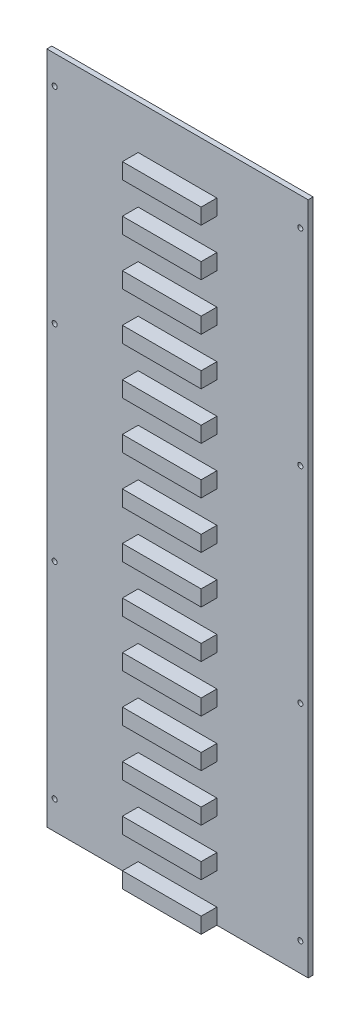
SolidWorks part; units mm, degrees
ref_plane "Front Plane" through (0, 0, 0) normal (0, 0, 1) x (1, 0, 0)
ref_plane "Top Plane" through (0, 0, 0) normal (0, 1, 0) x (1, 0, 0)
ref_plane "Right Plane" through (0, 0, 0) normal (1, 0, 0) x (0, 0, -1)
sketch "Sketch1" plane through (0, 0, 0) normal (0, 0, 1) x (1, 0, 0)
  line L1 (-41.5, -107) -> (41.5, -107)
  line L2 (-41.5, -107) -> (-41.5, 107)
  line L3 (-41.5, 107) -> (41.5, 107)
  line L4 (41.5, -107) -> (41.5, 107)
  line L5 (-41.5, -107) -> (41.5, 107) construction
  line L6 (-41.5, 107) -> (41.5, -107) construction
  point P0 (0, 0)
  dimension "D1" = 83
  dimension "D2" = 214
extrude "Boss-Extrude1" add sketch "Sketch1" along normal blind 1.5875
sketch "Sketch2" plane through (0, 0, 1.5875) normal (0, 0, 1) x (1, 0, 0)
  line L0 (0, -107) -> (0, 107) construction
  line L1 (-12.5, 88) -> (12.5, 88)
  line L2 (-12.5, 88) -> (-12.5, 93)
  line L3 (-12.5, 93) -> (12.5, 93)
  line L4 (12.5, 88) -> (12.5, 93)
  line L5 (-12.5, 88) -> (12.5, 93) construction
  line L6 (-12.5, 93) -> (12.5, 88) construction
  line L7 (41.5, 107) -> (-41.5, 107) construction
  line L8 (-12.5, 73) -> (12.5, 73)
  line L9 (-12.5, 73) -> (-12.5, 78)
  line L10 (-12.5, 78) -> (12.5, 78)
  line L11 (12.5, 73) -> (12.5, 78)
  line L12 (-12.5, 73) -> (12.5, 78) construction
  line L13 (-12.5, 78) -> (12.5, 73) construction
  line L14 (-12.5, 58) -> (12.5, 58)
  line L15 (-12.5, 58) -> (-12.5, 63)
  line L16 (-12.5, 63) -> (12.5, 63)
  line L17 (12.5, 58) -> (12.5, 63)
  line L18 (-12.5, 58) -> (12.5, 63) construction
  line L19 (-12.5, 63) -> (12.5, 58) construction
  line L20 (-12.5, 43) -> (12.5, 43)
  line L21 (-12.5, 43) -> (-12.5, 48)
  line L22 (-12.5, 48) -> (12.5, 48)
  line L23 (12.5, 43) -> (12.5, 48)
  line L24 (-12.5, 43) -> (12.5, 48) construction
  line L25 (-12.5, 48) -> (12.5, 43) construction
  line L26 (-12.5, 28) -> (12.5, 28)
  line L27 (-12.5, 28) -> (-12.5, 33)
  line L28 (-12.5, 33) -> (12.5, 33)
  line L29 (12.5, 28) -> (12.5, 33)
  line L30 (-12.5, 28) -> (12.5, 33) construction
  line L31 (-12.5, 33) -> (12.5, 28) construction
  line L32 (-12.5, 13) -> (12.5, 13)
  line L33 (-12.5, 13) -> (-12.5, 18)
  line L34 (-12.5, 18) -> (12.5, 18)
  line L35 (12.5, 13) -> (12.5, 18)
  line L36 (-12.5, 13) -> (12.5, 18) construction
  line L37 (-12.5, 18) -> (12.5, 13) construction
  line L38 (-12.5, -2) -> (12.5, -2)
  line L39 (-12.5, -2) -> (-12.5, 3)
  line L40 (-12.5, 3) -> (12.5, 3)
  line L41 (12.5, -2) -> (12.5, 3)
  line L42 (-12.5, -2) -> (12.5, 3) construction
  line L43 (-12.5, 3) -> (12.5, -2) construction
  line L44 (-12.5, -17) -> (12.5, -17)
  line L45 (-12.5, -17) -> (-12.5, -12)
  line L46 (-12.5, -12) -> (12.5, -12)
  line L47 (12.5, -17) -> (12.5, -12)
  line L48 (-12.5, -17) -> (12.5, -12) construction
  line L49 (-12.5, -12) -> (12.5, -17) construction
  line L50 (-12.5, -32) -> (12.5, -32)
  line L51 (-12.5, -32) -> (-12.5, -27)
  line L52 (-12.5, -27) -> (12.5, -27)
  line L53 (12.5, -32) -> (12.5, -27)
  line L54 (-12.5, -32) -> (12.5, -27) construction
  line L55 (-12.5, -27) -> (12.5, -32) construction
  line L56 (-12.5, -47) -> (12.5, -47)
  line L57 (-12.5, -47) -> (-12.5, -42)
  line L58 (-12.5, -42) -> (12.5, -42)
  line L59 (12.5, -47) -> (12.5, -42)
  line L60 (-12.5, -47) -> (12.5, -42) construction
  line L61 (-12.5, -42) -> (12.5, -47) construction
  line L62 (-12.5, -62) -> (12.5, -62)
  line L63 (-12.5, -62) -> (-12.5, -57)
  line L64 (-12.5, -57) -> (12.5, -57)
  line L65 (12.5, -62) -> (12.5, -57)
  line L66 (-12.5, -62) -> (12.5, -57) construction
  line L67 (-12.5, -57) -> (12.5, -62) construction
  line L68 (-12.5, -77) -> (12.5, -77)
  line L69 (-12.5, -77) -> (-12.5, -72)
  line L70 (-12.5, -72) -> (12.5, -72)
  line L71 (12.5, -77) -> (12.5, -72)
  line L72 (-12.5, -77) -> (12.5, -72) construction
  line L73 (-12.5, -72) -> (12.5, -77) construction
  line L74 (-12.5, -92) -> (12.5, -92)
  line L75 (-12.5, -92) -> (-12.5, -87)
  line L76 (-12.5, -87) -> (12.5, -87)
  line L77 (12.5, -92) -> (12.5, -87)
  line L78 (-12.5, -92) -> (12.5, -87) construction
  line L79 (-12.5, -87) -> (12.5, -92) construction
  line L80 (-12.5, -107) -> (12.5, -107)
  line L81 (-12.5, -107) -> (-12.5, -102)
  line L82 (-12.5, -102) -> (12.5, -102)
  line L83 (12.5, -107) -> (12.5, -102)
  line L84 (-12.5, -107) -> (12.5, -102) construction
  line L85 (-12.5, -102) -> (12.5, -107) construction
  point P0 (0, 90.5)
  point P5 (0, -29.5)
  point P11 (0, 0)
  point P13 (0, 75.5)
  point P18 (0, 60.5)
  point P23 (0, 45.5)
  point P28 (0, 30.5)
  point P33 (0, 15.5)
  point P38 (0, 0.5)
  point P43 (0, -14.5)
  point P51 (0, -44.5)
  point P56 (0, -59.5)
  point P61 (0, -74.5)
  point P66 (0, -89.5)
  point P71 (0, -104.5)
  dimension "D1" = 25
  dimension "D2" = 5
  dimension "D3" = 19
  dimension "D5" = 15
  dimension "D4" = 14
extrude "Boss-Extrude2" add sketch "Sketch2" along normal blind 5
hole_wizard "#0 Clearance Hole1" positions "Sketch5" profile "Sketch3" hole size "#0" standard "ANSI Inch"
sketch "Sketch5" plane through (0, 0, 1.5875) normal (0, 0, 1) x (1, 0, 0)
  line L0 (0, 0) -> (0, 107) construction
  line L1 (41.5, 107) -> (-41.5, 107) construction
  line L4 (-41.5, 107) -> (-41.5, -107) construction
  line L5 (-41.5, 0) -> (41.5, 0) construction
  line L6 (41.5, -107) -> (41.5, 107) construction
  point P490 (-39, 98)
  point P492 (39, 98)
  point P533 (-39, 32.6667)
  point P534 (39, 32.6667)
  point P535 (-39, -32.6667)
  point P536 (39, -32.6667)
  point P537 (-39, -98)
  point P538 (39, -98)
  dimension "D1" = 2.5
  dimension "D2" = 4
  dimension "D3" = 196
sketch "Sketch3" plane through (-39, 98, 1.5875) normal (1, 0, 0) x (0, -1, 0)
  line L0 (0, 0) -> (0, 3.6596)
  line L1 (0, 3.6596) -> (0.8064, 3.175)
  line L2 (0.8064, 3.175) -> (0.8064, 0)
  line L5 (0.8064, 0) -> (0, 0)
  line L10 (0, 3.6596) -> (-0.8065, 3.175) construction
  line L11 (0, -6.35) -> (0, 107.95) construction
  dimension "Hole Dia." = 1.6129
  dimension "Hole Depth" = 3.175
  dimension "Drill Angle" = 118
